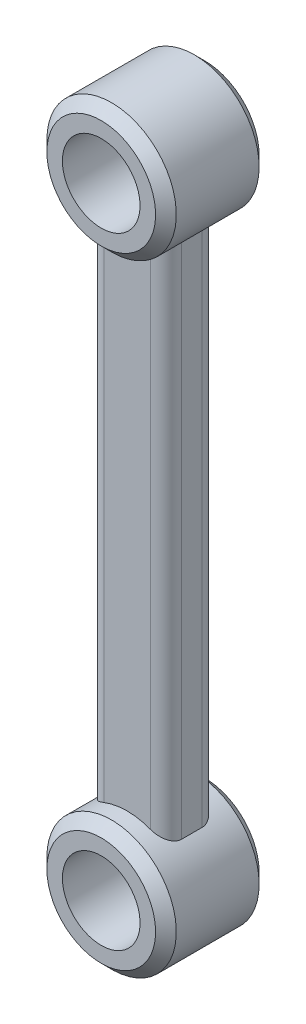
SolidWorks part; units mm, degrees
ref_plane "Front Plane" through (0, 0, 0) normal (0, 0, 1) x (1, 0, 0)
ref_plane "Top Plane" through (0, 0, 0) normal (0, 1, 0) x (1, 0, 0)
ref_plane "Right Plane" through (0, 0, 0) normal (1, 0, 0) x (0, 0, -1)
sketch "Sketch2" plane through (0, 0, 0) normal (0, 0, 1) x (1, 0, 0)
  line L1 (-9.525, 12.7) -> (-9.525, 139.7)
  line L2 (9.525, 12.7) -> (9.525, 139.7)
  arc A2 (9.525, 139.7) -> (-9.525, 139.7) centre (0, 152.4) ccw
  arc A3 (-9.525, 12.7) -> (9.525, 12.7) centre (0, 0) ccw
  point P3 (0, 76.2)
  dimension "D3" = 31.75
  dimension "D4" = 31.75
extrude "Boss-Extrude1" add sketch "Sketch2" along normal blind 12.7
sketch "Sketch3" plane through (0, 0, 0) normal (0, 0, -1) x (-1, 0, 0)
  circle A0 centre (0, 152.4) radius 15.875
  circle A1 centre (0, 0) radius 15.875
extrude "Boss-Extrude2" add sketch "Sketch3" along normal blind 6.35 and the other way blind 19.05
fillet "Fillet1" radius 3.81 4 edges at (-9.525, 76.2, 12.7) (-9.525, 76.2, 0) (9.525, 76.2, 12.7) (9.525, 76.2, 0)
sketch "Sketch4" plane through (0, 0, -6.35) normal (0, 0, -1) x (-1, 0, 0)
  circle A0 centre (0, 152.4) radius 9.525
  circle A1 centre (0, 0) radius 9.525
  dimension "D1" = 19.05
  dimension "D2" = 19.05
extrude "Cut-Extrude1" cut sketch "Sketch4" against normal blind 52.578
chamfer "Chamfer1" distance 2.54 angle 45 4 edges at (-15.875, 0, 19.05) (-15.875, 0, -6.35) (-15.875, 152.4, 19.05) (-15.875, 152.4, -6.35)
